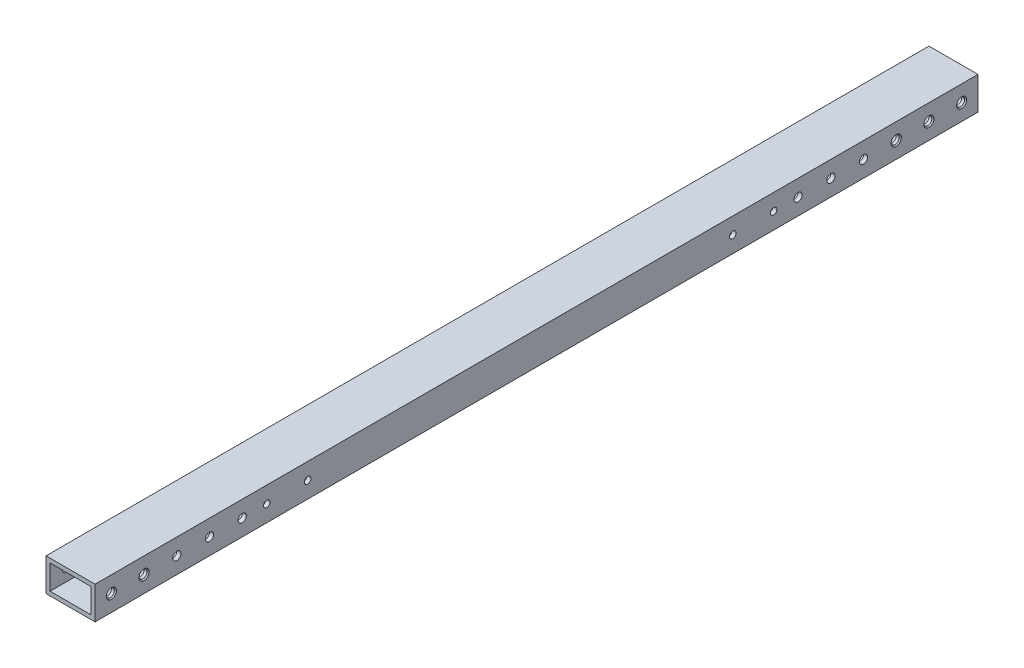
SolidWorks part; units mm, degrees
ref_plane "Front Plane" through (0, 0, 0) normal (0, 0, 1) x (1, 0, 0)
ref_plane "Top Plane" through (0, 0, 0) normal (0, 1, 0) x (1, 0, 0)
ref_plane "Right Plane" through (0, 0, 0) normal (1, 0, 0) x (0, 0, -1)
sketch "Sketch1" plane through (0, 0, 0) normal (0, 0, 1) x (1, 0, 0)
  line L0 (-15.875, 9.525) -> (15.875, 9.525)
  line L2 (-19.05, 12.7) -> (19.05, 12.7)
  line L3 (-19.05, 12.7) -> (-19.05, -12.7)
  line L4 (-19.05, -12.7) -> (19.05, -12.7)
  line L5 (19.05, 12.7) -> (19.05, -12.7)
  line L10 (15.875, 9.525) -> (15.875, -9.525)
  line L11 (-15.875, -9.525) -> (15.875, -9.525)
  line L12 (-15.875, 9.525) -> (-15.875, -9.525)
  point P12 (0, 12.7)
  point P14 (19.05, 0)
  dimension "Wall Thickness" = 3.175
  dimension "Outside Width" = 38.1
  dimension "Outside Height" = 25.4
  dimension "Inside Height" = 19.05
  dimension "Inside Width" = 31.75
sketch "Sketch2" plane through (0, 0, 0) normal (1, 0, 0) x (0, 0, -1)
  line L0 (342.9, 0) -> (-342.9, 0)
  point P4 (0, 0)
  point P7 (-342.9, 0)
  point P10 (342.9, 0)
  dimension "Length" = 685.8
sketch "Sketch3" plane through (0, 0, 0) normal (0, 0, 1) x (1, 0, 0)
  line L21 (19.05, 12.7) -> (-19.05, 12.7)
  line L22 (19.05, -12.7) -> (19.05, 12.7)
  line L23 (-19.05, -12.7) -> (19.05, -12.7)
  line L24 (-19.05, 12.7) -> (-19.05, -12.7)
  line L25 (19.05, 12.7) -> (-19.05, 12.7)
  line L26 (19.05, -12.7) -> (19.05, 12.7)
  line L27 (-19.05, -12.7) -> (19.05, -12.7)
  line L28 (-19.05, 12.7) -> (-19.05, -12.7)
  line L29 (15.875, 9.525) -> (-15.875, 9.525)
  line L30 (15.875, -9.525) -> (15.875, 9.525)
  line L31 (-15.875, -9.525) -> (15.875, -9.525)
  line L32 (-15.875, 9.525) -> (-15.875, -9.525)
  line L33 (15.875, 9.525) -> (-15.875, 9.525)
  line L34 (15.875, -9.525) -> (15.875, 9.525)
  line L35 (-15.875, -9.525) -> (15.875, -9.525)
  line L36 (-15.875, 9.525) -> (-15.875, -9.525)
  dimension "D1" = 0
  dimension "D2" = 0
extrude "Boss-Extrude1" add sketch "Sketch3" along normal up to vertex (342.9 mm away) and the other way up to vertex (342.9 mm away) up to point (0, 0, 342.9) other way up to point (0, 0, -342.9)
sketch "Drawing Reference" plane through (0, 0, 0) normal (1, 0, 0) x (0, 0, -1)
  line L0 (-342.9, 0) -> (342.9, 0) construction
  line L1 (0, -12.7) -> (0, 12.7) construction
  line L2 (-342.9, -12.7) -> (342.9, -12.7) construction
  line L5 (-342.9, 12.7) -> (342.9, 12.7) construction
  point P7 (-315.468, 0)
  point P8 (315.468, 0)
  dimension "D1" = 27.432
sketch "Sketch4" plane through (-19.05, 0, 0) normal (-1, 0, 0) x (0, 0, 1)
  line L0 (-342.9, 0) -> (-330.2, 0)
  line L1 (-342.9, 12.7) -> (-342.9, -12.7) construction
  line L2 (-330.2, 0) -> (-304.8, 0)
  line L3 (-304.8, 0) -> (-279.4, 0)
  line L4 (-279.4, 0) -> (-254, 0)
  line L5 (-254, 0) -> (-228.6, 0)
  line L6 (-228.6, 0) -> (-203.2, 0)
  line L7 (342.9, 0) -> (330.2, 0)
  line L8 (342.9, 12.7) -> (342.9, -12.7) construction
  line L9 (330.2, 0) -> (304.8, 0)
  line L10 (304.8, 0) -> (279.4, 0)
  line L11 (279.4, 0) -> (254, 0)
  line L12 (254, 0) -> (228.6, 0)
  line L13 (-203.2, 0) -> (-184.15, 0)
  line L14 (-203.2, 0) -> (-152.4, 0) construction
  line L15 (228.6, 0) -> (209.55, 0)
  line L16 (228.6, 0) -> (177.8, 0) construction
hole_wizard "1/4 (0.25) Diameter Hole2" positions "Sketch7" profile "Sketch8" hole size "1/4" standard "ANSI Inch" end condition through all
sketch "Sketch7" plane through (-19.05, 0, 0) normal (-1, 0, 0) x (0, 0, 1)
  point P0 (-330.2, 0)
  point P3 (-304.8, 0)
  point P7 (330.2, 0)
  point P11 (-279.4, 0)
  point P14 (304.8, 0)
sketch "Sketch8" plane through (-19.05, 0, -330.2) normal (0, 1, 0) x (0, 0, 1)
  line L0 (0, 0) -> (0, 38.1)
  line L1 (0, 38.1) -> (3.9624, 38.1)
  line L2 (3.175, 37.1942) -> (3.175, 0)
  line L5 (3.175, 0) -> (0, 0)
  line L7 (3.9624, 38.1) -> (3.175, 37.1942)
  line L8 (-3.9624, 38.1) -> (-3.175, 37.1942) construction
  line L11 (0, -6.35) -> (0, 107.95) construction
  dimension "Thru Hole Dia." = 6.35
  dimension "Thru Hole Depth" = 38.1
  dimension "Far C'Sink Dia." = 7.9248
  dimension "Far C'Sink Angle" = 82
hole_wizard "1/4 (0.25) Diameter Hole3" positions "Sketch9" profile "Sketch10" hole size "1/4" standard "ANSI Inch" end condition through all
sketch "Sketch9" plane through (19.05, 0, 0) normal (1, 0, 0) x (0, 0, -1)
  point P0 (-279.4, 0)
  point P3 (-254, 0)
  point P6 (-228.6, 0)
  point P9 (254, 0)
  point P12 (228.6, 0)
  point P15 (203.2, 0)
sketch "Sketch10" plane through (19.05, 0, 279.4) normal (0, 1, 0) x (0, 0, -1)
  line L0 (0, 0) -> (0, 38.1)
  line L1 (0, 38.1) -> (3.175, 38.1)
  line L2 (3.175, 38.1) -> (3.175, 0)
  line L5 (3.175, 0) -> (0, 0)
  line L11 (0, -6.35) -> (0, 107.95) construction
  dimension "Thru Hole Dia." = 6.35
  dimension "Thru Hole Depth" = 38.1
hole_wizard "13/64 (0.20313) Diameter Hole1" positions "Sketch11" profile "Sketch12" hole size "13/64" standard "ANSI Inch" end condition through all
sketch "Sketch11" plane through (19.05, 0, 0) normal (1, 0, 0) x (0, 0, -1)
  point P0 (152.4, 0)
  point P7 (-177.8, 0)
sketch "Sketch12" plane through (19.05, 0, -152.4) normal (0, 1, 0) x (0, 0, -1)
  line L0 (0, 0) -> (0, 38.1)
  line L1 (0, 38.1) -> (2.5798, 38.1)
  line L2 (2.5798, 38.1) -> (2.5798, 0)
  line L5 (2.5798, 0) -> (0, 0)
  line L11 (0, -6.35) -> (0, 107.95) construction
  dimension "Thru Hole Dia." = 5.1595
  dimension "Thru Hole Depth" = 38.1
hole_wizard "#10 Clearance Hole1" positions "Sketch13" profile "Sketch14" hole size "#10" standard "ANSI Inch" end condition through all
sketch "Sketch13" plane through (-19.05, 0, 0) normal (-1, 0, 0) x (0, 0, 1)
  point P0 (-184.15, 0)
  point P3 (209.55, 0)
sketch "Sketch14" plane through (-19.05, 0, -184.15) normal (0, 1, 0) x (0, 0, 1)
  line L0 (0, 0) -> (0, 38.1)
  line L1 (0, 38.1) -> (2.4892, 38.1)
  line L2 (2.4892, 38.1) -> (2.4892, 0)
  line L5 (2.4892, 0) -> (0, 0)
  line L11 (0, -6.35) -> (0, 107.95) construction
  dimension "Thru Hole Dia." = 4.9784
  dimension "Thru Hole Depth" = 38.1
equation "\"D1@Drawing Reference\"=\"Outside Width@Sketch1\" * 0.72"
